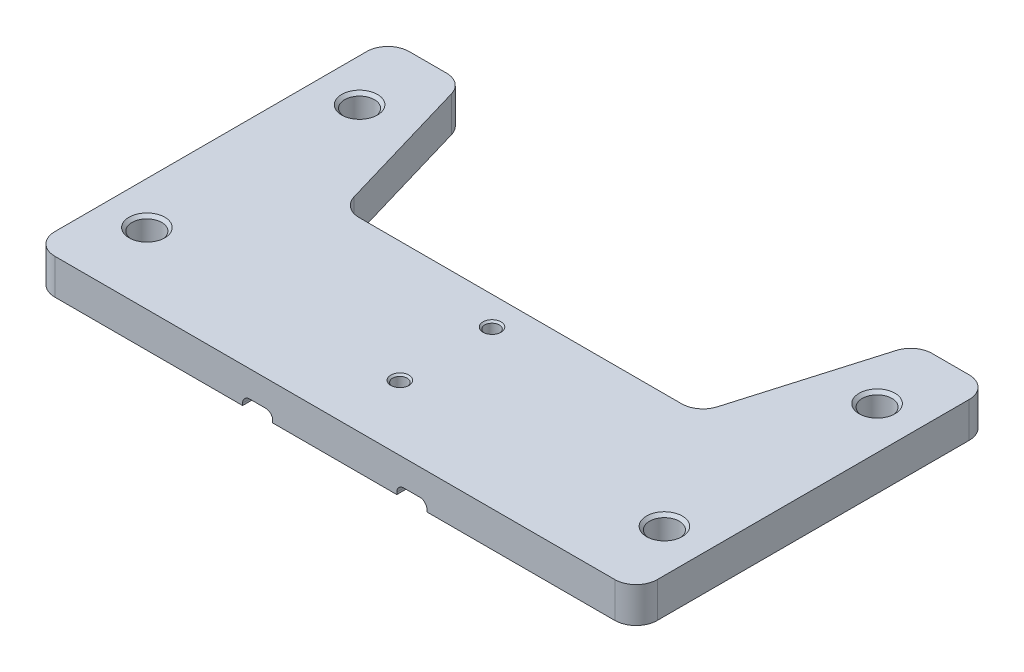
SolidWorks part; units mm, degrees
ref_plane "Front Plane" through (0, 0, 0) normal (0, 0, 1) x (1, 0, 0)
ref_plane "Top Plane" through (0, 0, 0) normal (0, 1, 0) x (1, 0, 0)
ref_plane "Right Plane" through (0, 0, 0) normal (1, 0, 0) x (0, 0, -1)
sketch "Sketch2" plane through (0, 0, 0) normal (0, 1, 0) x (1, 0, 0)
  line L1 (42.5, 0) -> (42.5, 50)
  line L2 (42.5, 50) -> (22.5, 50)
  line L3 (22.5, 50) -> (8.75, 26.1843)
  line L4 (8.75, 26.1843) -> (-8.75, 26.1843)
  line L5 (-8.75, 26.1843) -> (-22.5, 50)
  line L6 (-22.5, 50) -> (-42.5, 50)
  line L7 (-42.5, 50) -> (-42.5, 0)
  line L9 (-42.5, 0) -> (42.5, 0)
  point P0 (0, 26.1843)
  point P3 (0, 0)
  point P11 (32.5, 50)
  point P13 (-32.5, 50)
  dimension "D1" = 17.5
  dimension "D2" = 85
  dimension "D3" = 50
  dimension "D4" = 60
  dimension "D5" = 60
  dimension "D6" = 20
extrude "Boss-Extrude1" add sketch "Sketch2" along normal blind 5
sketch "Sketch3" plane through (0, 0, -26.1843) normal (0, 0, -1) x (-1, 0, 0)
  line L6 (-8.75, 0) -> (8.75, 0)
  line L7 (-8.75, 0) -> (-8.75, 1)
  line L8 (-8.75, 1) -> (8.75, 1)
  line L9 (8.75, 0) -> (8.75, 1)
  point P5 (0, 0)
  dimension "D1" = 17.5
  dimension "D2" = 1
extrude "Cut-Extrude1" [suppressed] cut sketch "Sketch3" against normal through all
hole_wizard "M2.5x0.45 Tapped Hole1" positions "Sketch4" profile "Sketch5" tap size "M2.5x0.45" standard "ANSI Metric"
sketch "Sketch4" plane through (0, 5, 0) normal (0, 1, 0) x (1, 0, 0)
  line L1 (8.75, 26.1843) -> (-8.75, 26.1843) construction
  point P0 (0, 9.1843)
  point P2 (0, 22.1843)
  dimension "D1" = 13
  dimension "D2" = 4
  dimension "D3" = 8.75
sketch "Sketch5" plane through (0, 5, -9.1843) normal (1, 0, 0) x (0, 0, 1)
  line L0 (0, 0) -> (0, 6.9659)
  line L1 (0, 6.9659) -> (1.025, 6.35)
  line L2 (1.025, 6.35) -> (1.025, 0.25)
  line L3 (1.025, 0.25) -> (1.275, 0)
  line L5 (1.275, 0) -> (0, 0)
  line L6 (-1.025, 0.25) -> (-1.275, 0) construction
  line L10 (0, 6.9659) -> (-1.025, 6.35) construction
  line L11 (0, -6.35) -> (0, 107.95) construction
  dimension "Tap Drill Dia." = 2.05
  dimension "Tap Drill Depth" = 6.35
  dimension "Near C'Sink Dia." = 2.55
  dimension "Near C'Sink Angle" = 90
  dimension "Drill Angle" = 118
cosmetic thread "Hole Thread1" parameters "D1"=5, "D2"=2.5
cosmetic thread "Hole Thread2" parameters "D1"=5, "D2"=2.5
hole_wizard "M5x0.8 Tapped Hole1" positions "Sketch6" profile "Sketch7" tap size "M5x0.8" standard "ANSI Metric"
sketch "Sketch6" plane through (0, 5, 0) normal (0, 1, 0) x (1, 0, 0)
  line L1 (-22.5, 50) -> (-42.5, 50) construction
  line L2 (42.5, 50) -> (22.5, 50) construction
  line L3 (42.5, 0) -> (42.5, 50) construction
  line L4 (-42.5, 50) -> (-42.5, 0) construction
  line L5 (-42.5, 0) -> (42.5, 0) construction
  point P0 (-36.5, 40)
  point P2 (36.5, 40)
  point P18 (-36.5, 10)
  point P20 (36.5, 10)
  dimension "D1" = 6
  dimension "D2" = 10
  dimension "D3" = 10
  dimension "D4" = 6
  dimension "D5" = 10
  dimension "D6" = 10
sketch "Sketch7" plane through (-36.5, 5, -40) normal (1, 0, 0) x (0, 0, 1)
  line L0 (0, 0) -> (0, 13.6618)
  line L1 (0, 13.6618) -> (2.1, 12.4)
  line L2 (2.1, 12.4) -> (2.1, 0.425)
  line L3 (2.1, 0.425) -> (2.525, 0)
  line L5 (2.525, 0) -> (0, 0)
  line L6 (-2.1, 0.425) -> (-2.525, 0) construction
  line L10 (0, 13.6618) -> (-2.1, 12.4) construction
  line L11 (0, -6.35) -> (0, 107.95) construction
  dimension "Tap Drill Dia." = 4.2
  dimension "Tap Drill Depth" = 12.4
  dimension "Near C'Sink Dia." = 5.05
  dimension "Near C'Sink Angle" = 90
  dimension "Drill Angle" = 118
cosmetic thread "Hole Thread3" parameters "D1"=10, "D2"=5
cosmetic thread "Hole Thread4" parameters "D1"=10, "D2"=5
cosmetic thread "Hole Thread5" parameters "D1"=10, "D2"=5
cosmetic thread "Hole Thread6" parameters "D1"=10, "D2"=5
sketch "Sketch8" plane through (0, 0, -26.1843) normal (0, 0, -1) x (-1, 0, 0)
  line L5 (-8.75, 5) -> (-8.75, 0) construction
  line L6 (-13, 0) -> (-8.75, 0)
  line L7 (-13, 0) -> (-13, 1.3)
  line L8 (-13, 1.3) -> (-8.75, 1.3)
  line L9 (-8.75, 0) -> (-8.75, 1.3)
  line L10 (0, 0) -> (0, 12.6228) construction
  line L11 (8.75, 0) -> (8.75, 1.3)
  line L12 (13, 1.3) -> (8.75, 1.3)
  line L13 (13, 0) -> (13, 1.3)
  line L14 (13, 0) -> (8.75, 0)
  line L15 (-22.5, 0) -> (-8.75, 0) construction
  dimension "D1" = 4.25
  dimension "D2" = 1.3
extrude "Cut-Extrude2" cut sketch "Sketch8" against normal through all both and the other way through all
sketch "Sketch9" plane through (0, 0, 0) normal (0, -1, 0) x (1, 0, 0)
  line L0 (-32, -50) -> (-25, -26.1843)
  line L1 (-22.5, -50) -> (-42.5, -50) construction
  line L3 (25, -26.1843) -> (32, -50)
  line L4 (42.5, -50) -> (22.5, -50) construction
  line L5 (32, -50) -> (-32, -50)
  line L6 (-25, -26.1843) -> (25, -26.1843)
  line L7 (8.75, -26.1843) -> (-8.75, -26.1843) construction
  point P8 (0, -50)
  point P12 (0, -26.1843)
  dimension "D1" = 64
  dimension "D2" = 50
extrude "Cut-Extrude3" cut sketch "Sketch9" against normal through all
fillet "Fillet1" radius 3 8 edges at (42.5, 2.5, -50) (-42.5, 2.5, -50) (-32, 2.5, -50) (32, 2.5, -50) (25, 2.5, -26.1843) (-25, 2.5, -26.1843) (42.5, 2.5, 0) (-42.5, 2.5, 0)
fillet "Fillet2" radius 1 4 edges at (-13, 1.3, -13.0922) (-8.75, 1.3, -13.0922) (8.75, 1.3, -13.0922) (13, 1.3, -13.0922)
